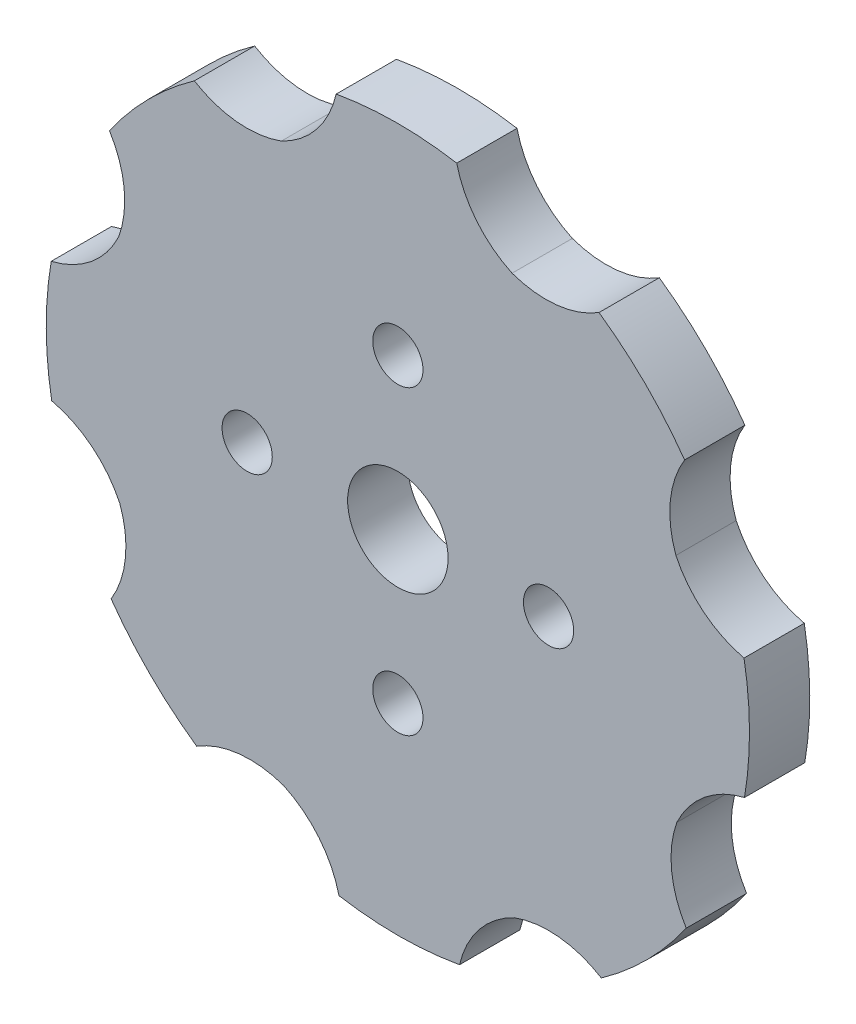
SolidWorks part; units mm, degrees
ref_plane "Front Plane" through (0, 0, 0) normal (0, 0, 1) x (1, 0, 0)
ref_plane "Top Plane" through (0, 0, 0) normal (0, 1, 0) x (1, 0, 0)
ref_plane "Right Plane" through (0, 0, 0) normal (1, 0, 0) x (0, 0, -1)
sketch "Sketch1" plane through (0, 0, 0) normal (0, 0, 1) x (1, 0, 0)
  line L0 (0, 42.5738) -> (0, 0) construction
  line L1 (-6.1404, 34.4572) -> (-7.0756, 29.1537)
  line L2 (5.8596, 34.506) -> (6.7915, 29.2211)
  line L3 (20.023, 28.7068) -> (15.6116, 25.6179)
  line L4 (28.5428, 20.256) -> (25.4648, 15.8601)
  line L5 (34.4572, 6.1404) -> (29.1537, 7.0756)
  line L6 (34.506, -5.8596) -> (29.2211, -6.7915)
  line L7 (28.7068, -20.023) -> (25.6179, -15.6116)
  line L8 (20.256, -28.5428) -> (15.8601, -25.4648)
  line L9 (6.1404, -34.4572) -> (7.0756, -29.1537)
  line L10 (-5.8596, -34.506) -> (-6.7915, -29.2211)
  line L11 (-20.023, -28.7068) -> (-15.6116, -25.6179)
  line L12 (-28.5428, -20.256) -> (-25.4648, -15.8601)
  line L13 (-34.4572, -6.1404) -> (-29.1537, -7.0756)
  line L14 (-34.506, 5.8596) -> (-29.2211, 6.7915)
  line L15 (-28.7068, 20.023) -> (-25.6179, 15.6116)
  line L16 (-20.256, 28.5428) -> (-15.8601, 25.4648)
  line L17 (0, 0) -> (-15, 0) construction
  line L18 (0, 0) -> (0, -25.6179) construction
  arc A0 (5.8596, 34.506) -> (-6.1404, 34.4572) centre (0, 0) ccw
  arc A1 (-29.1537, -7.0756) -> (-25.4648, -15.8601) centre (0, 0) ccw
  arc A2 (28.5428, 20.256) -> (20.023, 28.7068) centre (0, 0) ccw
  arc A3 (34.506, -5.8596) -> (34.4572, 6.1404) centre (0, 0) ccw
  arc A4 (20.256, -28.5428) -> (28.7068, -20.023) centre (0, 0) ccw
  arc A5 (-5.8596, -34.506) -> (6.1404, -34.4572) centre (0, 0) ccw
  arc A6 (-28.5428, -20.256) -> (-20.023, -28.7068) centre (0, 0) ccw
  arc A7 (-34.506, 5.8596) -> (-34.4572, -6.1404) centre (0, 0) ccw
  arc A8 (-20.256, 28.5428) -> (-28.7068, 20.023) centre (0, 0) ccw
  circle A9 centre (0, 15) radius 2.5
  circle A10 centre (15, 0) radius 2.5
  circle A11 centre (0, -15) radius 2.5
  circle A12 centre (-15, 0) radius 2.5
  circle A13 centre (0, 0) radius 5
  arc A14 (-15.6116, -25.6179) -> (-6.7915, -29.2211) centre (0, 0) ccw
  arc A15 (7.0756, -29.1537) -> (15.8601, -25.4648) centre (0, 0) ccw
  arc A16 (25.6179, -15.6116) -> (29.2211, -6.7915) centre (0, 0) ccw
  arc A17 (29.1537, 7.0756) -> (25.4648, 15.8601) centre (0, 0) ccw
  arc A18 (15.6116, 25.6179) -> (6.7915, 29.2211) centre (0, 0) ccw
  arc A19 (-7.0756, 29.1537) -> (-15.8601, 25.4648) centre (0, 0) ccw
  arc A20 (-25.6179, 15.6116) -> (-29.2211, 6.7915) centre (0, 0) ccw
  point P41 (0, 0)
  point P50 (0, 0)
  dimension "D1" = 70
  dimension "D3" = 12.0001
  dimension "D2" = 60
  dimension "D8" = 5
  dimension "D11" = 10
  dimension "D4" = 10
  dimension "D5" = 10
  dimension "D6" = 5.2849
  dimension "D9" = 15
  dimension "D7" = 8
  dimension "D10" = 4
extrude "Boss-Extrude1" add sketch "Sketch1" along normal blind 6
fillet "Fillet1" radius 10 16 edges at (6.7915, 29.2211, 3) (15.6116, 25.6179, 3) (25.4648, 15.8601, 3) (29.1537, 7.0756, 3) (29.2211, -6.7915, 3) (25.6179, -15.6116, 3) (15.8601, -25.4648, 3) (7.0756, -29.1537, 3) (-6.7915, -29.2211, 3) (-15.6116, -25.6179, 3) (-25.4648, -15.8601, 3) (-29.1537, -7.0756, 3) (-29.2211, 6.7915, 3) (-25.6179, 15.6116, 3) (-15.8601, 25.4648, 3) (-7.0756, 29.1537, 3)
